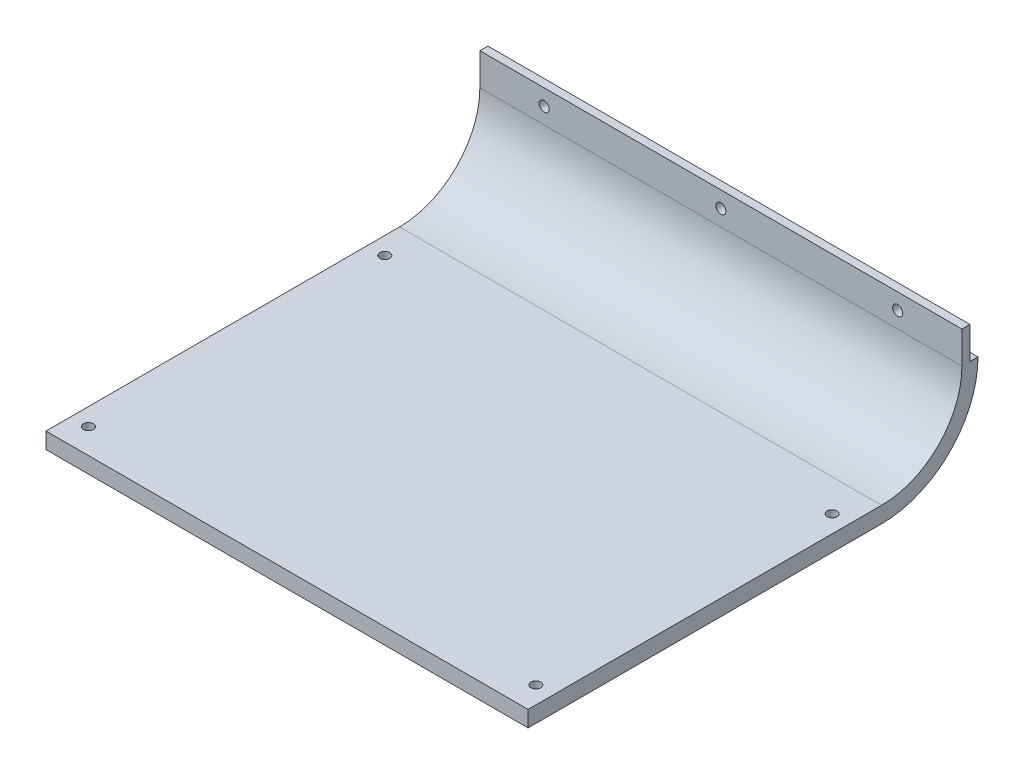
SolidWorks part; units mm, degrees
material "6061-T6 Aluminum"
ref_plane "Front Plane" through (0, 0, 0) normal (0, 0, 1) x (1, 0, 0)
ref_plane "Top Plane" through (0, 0, 0) normal (0, 1, 0) x (1, 0, 0)
ref_plane "Right Plane" through (0, 0, 0) normal (1, 0, 0) x (0, 0, -1)
sketch "Sketch1" plane through (0, 0, 0) normal (1, 0, 0) x (0, 0, -1)
  line L0 (-139.7, 0) -> (139.7, 0)
  line L5 (139.7, 0) -> (139.7, 12.7) construction
  line L7 (-139.7, 12.7) -> (139.7, 12.7)
  line L9 (-139.7, 0) -> (-139.7, 12.7)
  line L12 (139.7, 0) -> (139.7, 152.4) construction
  line L13 (0.6365, 139.0796) -> (-139.7417, 139.9778) construction
  line L14 (-12.6991, 151.8652) -> (-139.6605, 152.6775) construction
  line L15 (203.2, 76.2) -> (215.9, 76.2)
  arc A2 (139.7, 0) -> (-12.6991, 151.8652) centre (139.7, 152.4) ccw construction
  arc A3 (139.7, 12.7) -> (0.6365, 139.0796) centre (139.7, 152.4) ccw construction
  circle A5 centre (139.7, 76.2) radius 76.2 construction
  arc A6 (215.9, 76.2) -> (139.7, 0) centre (139.7, 76.2) cw
  circle A7 centre (139.7, 76.2) radius 63.5 construction
  arc A8 (203.2, 76.2) -> (139.7, 12.7) centre (139.7, 76.2) cw
  point P3 (0, 0)
  dimension "D1" = 152.4
  dimension "D2" = 12.7
  dimension "D4" = 127
  dimension "D6" = 12.7
  dimension "D3" = 12.7
  dimension "D5" = 12.7
  dimension "D7" = 355.6
extrude "Boss-Extrude1" add sketch "Sketch1" along normal blind 190.5 and the other way blind 190.5
sketch "Sketch2" plane through (0, 76.2, 0) normal (0, 1, 0) x (1, 0, 0)
  line L0 (-190.5, 215.9) -> (-190.5, 203.2) construction
  line L1 (-190.5, 209.55) -> (190.5, 209.55)
  line L2 (-190.5, 209.55) -> (-190.5, 203.2)
  line L3 (-190.5, 203.2) -> (190.5, 203.2)
  line L4 (190.5, 209.55) -> (190.5, 203.2)
extrude "Boss-Extrude2" add sketch "Sketch2" along normal blind 25.4
sketch "Sketch3" plane through (0, 0, -209.55) normal (0, 0, -1) x (-1, 0, 0)
  line L0 (-190.5, 88.9) -> (190.5, 88.9) construction
  line L1 (-190.5, 101.6) -> (-190.5, 76.2) construction
  line L2 (190.5, 101.6) -> (190.5, 76.2) construction
  line L3 (-139.7, 101.6) -> (-139.7, 76.2) construction
  line L4 (-190.5, 101.6) -> (190.5, 101.6) construction
  line L5 (-190.5, 76.2) -> (190.5, 76.2) construction
  line L6 (0, 101.6) -> (0, 76.2) construction
  line L7 (190.5, 76.2) -> (-190.5, 76.2) construction
  line L8 (139.7, 101.6) -> (139.7, 76.2) construction
  circle A0 centre (-139.7, 88.9) radius 3.9687
  circle A1 centre (139.7, 88.9) radius 3.9687
  circle A2 centre (0, 88.9) radius 3.9687
  dimension "D3" = 7.9375
  dimension "D1" = 139.7
  dimension "D2" = 139.7
extrude "Cut-Extrude1" cut sketch "Sketch3" against normal blind 25.4
sketch "Sketch4" plane through (0, 12.7, 0) normal (0, 1, 0) x (1, 0, 0)
  line L0 (0, -139.7) -> (0, -119.888) construction
  line L1 (-190.5, -139.7) -> (190.5, -139.7) construction
  line L2 (0, -119.888) -> (0, 0) construction
  line L3 (0, 0) -> (0, 114.3) construction
  line L6 (-176.784, 114.3) -> (176.784, 114.3) construction
  line L7 (-176.784, 0) -> (176.784, 0) construction
  line L8 (-176.784, -119.888) -> (176.784, -119.888) construction
  line L10 (190.5, 139.7) -> (190.5, -139.7) construction
  circle A0 centre (176.784, -119.888) radius 3.937
  circle A2 centre (176.784, 114.3) radius 3.937
  circle A3 centre (-176.784, -119.888) radius 3.937
  circle A5 centre (-176.784, 114.3) radius 3.937
  point P12 (0, 114.3)
  point P15 (0, 0)
  point P19 (0, -119.888)
  dimension "D3" = 7.874
  dimension "D4" = 254
  dimension "D1" = 19.812
  dimension "D2" = 13.716
extrude "Cut-Extrude2" cut sketch "Sketch4" against normal through all
